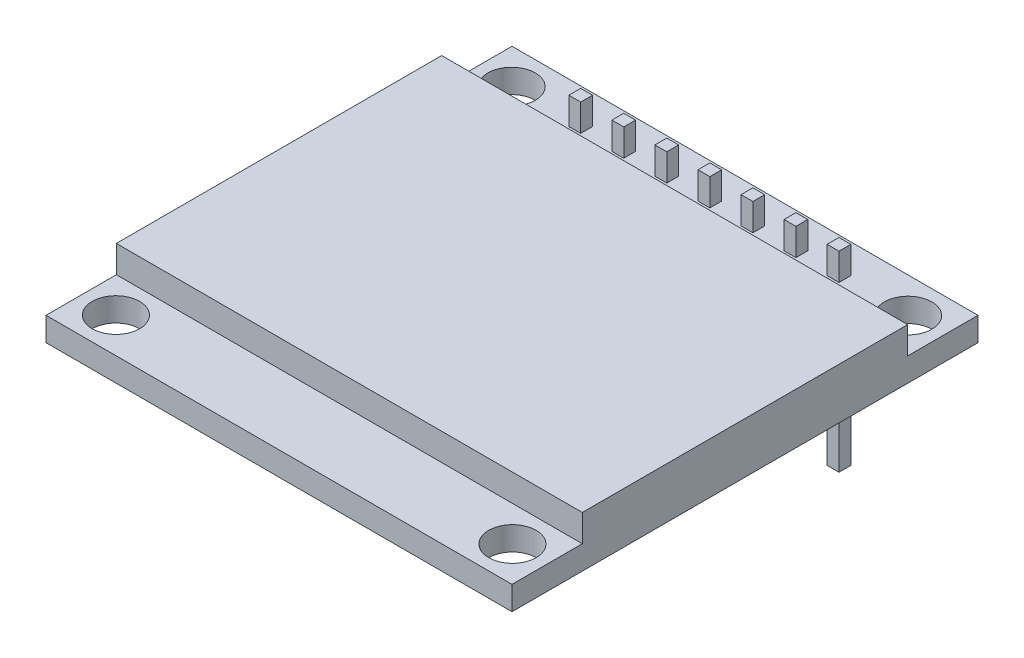
SolidWorks part; units mm, degrees
ref_plane "前视基准面" through (0, 0, 0) normal (0, 0, 1) x (1, 0, 0)
ref_plane "上视基准面" through (0, 0, 0) normal (0, 1, 0) x (1, 0, 0)
ref_plane "右视基准面" through (0, 0, 0) normal (1, 0, 0) x (0, 0, -1)
other "Configuration Table"
sketch "草图1" plane through (0, 0, 0) normal (0, 1, 0) x (1, 0, 0)
  line L0 (13.75, -23.35) -> (13.75, -27.5)
  line L1 (0, 0) -> (27.5, 0)
  line L2 (0, 0) -> (0, -27.5)
  line L3 (0, -27.5) -> (27.5, -27.5)
  line L4 (27.5, 0) -> (27.5, -27.5)
  line L9 (0, -4.15) -> (27.5, -4.15)
  line L10 (0, -4.15) -> (0, -23.35)
  line L11 (0, -23.35) -> (27.5, -23.35)
  line L12 (27.5, -4.15) -> (27.5, -23.35)
  line L13 (7.4, -0.805) -> (9.94, -0.805)
  line L18 (4.86, -0.805) -> (7.4, -0.805)
  line L19 (4.86, -0.805) -> (4.86, -3.345)
  line L20 (4.86, -3.345) -> (7.4, -3.345)
  line L21 (7.4, -0.805) -> (7.4, -3.345)
  line L22 (4.86, -0.805) -> (7.4, -3.345) construction
  line L23 (4.86, -3.345) -> (7.4, -0.805) construction
  line L24 (5.78, -2.425) -> (6.48, -2.425)
  line L25 (5.78, -2.425) -> (5.78, -1.725)
  line L26 (5.78, -1.725) -> (6.48, -1.725)
  line L27 (6.48, -2.425) -> (6.48, -1.725)
  line L28 (5.78, -2.425) -> (6.48, -1.725) construction
  line L29 (5.78, -1.725) -> (6.48, -2.425) construction
  line L30 (7.4, -0.805) -> (7.4, -3.345)
  line L31 (7.4, -3.345) -> (9.94, -3.345)
  line L32 (9.94, -0.805) -> (9.94, -3.345)
  line L33 (8.32, -2.425) -> (9.02, -2.425)
  line L34 (8.32, -2.425) -> (8.32, -1.725)
  line L35 (8.32, -1.725) -> (9.02, -1.725)
  line L36 (9.02, -2.425) -> (9.02, -1.725)
  line L37 (7.4, -0.805) -> (9.94, -3.345) construction
  line L38 (7.4, -3.345) -> (9.94, -0.805) construction
  line L39 (8.32, -2.425) -> (9.02, -1.725) construction
  line L40 (8.32, -1.725) -> (9.02, -2.425) construction
  line L41 (9.94, -0.805) -> (12.48, -0.805)
  line L42 (9.94, -0.805) -> (9.94, -3.345)
  line L43 (9.94, -3.345) -> (12.48, -3.345)
  line L44 (12.48, -0.805) -> (12.48, -3.345)
  line L45 (10.86, -2.425) -> (11.56, -2.425)
  line L46 (10.86, -2.425) -> (10.86, -1.725)
  line L47 (10.86, -1.725) -> (11.56, -1.725)
  line L48 (11.56, -2.425) -> (11.56, -1.725)
  line L49 (9.94, -0.805) -> (12.48, -3.345) construction
  line L50 (9.94, -3.345) -> (12.48, -0.805) construction
  line L51 (10.86, -2.425) -> (11.56, -1.725) construction
  line L52 (10.86, -1.725) -> (11.56, -2.425) construction
  line L53 (12.48, -0.805) -> (15.02, -0.805)
  line L54 (12.48, -0.805) -> (12.48, -3.345)
  line L55 (12.48, -3.345) -> (15.02, -3.345)
  line L56 (15.02, -0.805) -> (15.02, -3.345)
  line L57 (13.4, -2.425) -> (14.1, -2.425)
  line L58 (13.4, -2.425) -> (13.4, -1.725)
  line L59 (13.4, -1.725) -> (14.1, -1.725)
  line L60 (14.1, -2.425) -> (14.1, -1.725)
  line L61 (12.48, -0.805) -> (15.02, -3.345) construction
  line L62 (12.48, -3.345) -> (15.02, -0.805) construction
  line L63 (13.4, -2.425) -> (14.1, -1.725) construction
  line L64 (13.4, -1.725) -> (14.1, -2.425) construction
  line L65 (15.02, -0.805) -> (17.56, -0.805)
  line L66 (15.02, -0.805) -> (15.02, -3.345)
  line L67 (15.02, -3.345) -> (17.56, -3.345)
  line L68 (17.56, -0.805) -> (17.56, -3.345)
  line L69 (15.94, -2.425) -> (16.64, -2.425)
  line L70 (15.94, -2.425) -> (15.94, -1.725)
  line L71 (15.94, -1.725) -> (16.64, -1.725)
  line L72 (16.64, -2.425) -> (16.64, -1.725)
  line L73 (15.02, -0.805) -> (17.56, -3.345) construction
  line L74 (15.02, -3.345) -> (17.56, -0.805) construction
  line L75 (15.94, -2.425) -> (16.64, -1.725) construction
  line L76 (15.94, -1.725) -> (16.64, -2.425) construction
  line L77 (17.56, -0.805) -> (20.1, -0.805)
  line L78 (17.56, -0.805) -> (17.56, -3.345)
  line L79 (17.56, -3.345) -> (20.1, -3.345)
  line L80 (20.1, -0.805) -> (20.1, -3.345)
  line L81 (18.48, -2.425) -> (19.18, -2.425)
  line L82 (18.48, -2.425) -> (18.48, -1.725)
  line L83 (18.48, -1.725) -> (19.18, -1.725)
  line L84 (19.18, -2.425) -> (19.18, -1.725)
  line L85 (17.56, -0.805) -> (20.1, -3.345) construction
  line L86 (17.56, -3.345) -> (20.1, -0.805) construction
  line L87 (18.48, -2.425) -> (19.18, -1.725) construction
  line L88 (18.48, -1.725) -> (19.18, -2.425) construction
  line L89 (20.1, -0.805) -> (22.64, -0.805)
  line L90 (20.1, -0.805) -> (20.1, -3.345)
  line L91 (20.1, -3.345) -> (22.64, -3.345)
  line L92 (22.64, -0.805) -> (22.64, -3.345)
  line L93 (21.02, -2.425) -> (21.72, -2.425)
  line L94 (21.02, -2.425) -> (21.02, -1.725)
  line L95 (21.02, -1.725) -> (21.72, -1.725)
  line L96 (21.72, -2.425) -> (21.72, -1.725)
  line L97 (20.1, -0.805) -> (22.64, -3.345) construction
  line L98 (20.1, -3.345) -> (22.64, -0.805) construction
  line L99 (21.02, -2.425) -> (21.72, -1.725) construction
  line L100 (21.02, -1.725) -> (21.72, -2.425) construction
  line L101 (23.6355, 0) -> (23.6355, -4.15)
  circle A0 centre (2.05, -2.075) radius 1.4
  circle A1 centre (25.45, -2.075) radius 1.4
  circle A2 centre (2.05, -25.425) radius 1.4
  circle A3 centre (25.45, -25.425) radius 1.4
  point P9 (0, -13.75)
  point P10 (0, -13.75)
  point P19 (13.75, -25.425)
  point P20 (6.13, -2.075)
  point P25 (6.13, -2.075)
  point P32 (23.6355, -2.075)
  point P33 (8.67, -2.075)
  point P38 (8.67, -2.075)
  point P43 (11.21, -2.075)
  point P48 (11.21, -2.075)
  point P53 (13.75, -2.075)
  point P58 (13.75, -2.075)
  point P63 (16.29, -2.075)
  point P68 (16.29, -2.075)
  point P73 (18.83, -2.075)
  point P78 (18.83, -2.075)
  point P83 (21.37, -2.075)
  point P88 (21.37, -2.075)
  dimension "D3" = 2.8
  dimension "D9" = 0.7
  dimension "D1" = 27.5
  dimension "D2" = 19.2
  dimension "D5" = 2.05
  dimension "D7" = 2.05
  dimension "D8" = 2.54
  dimension "D10" = 7
extrude "凸台-拉伸1" add sketch "草图1" along normal blind 1.4 contours L3 L4 L1 L2 | A0 | A1 | A2 | A3
extrude "凸台-拉伸2" add sketch "草图1<3>" along normal blind 3 contours L9 L12 L11 L10
sketch "草图1<3>" plane through (0, 0, 0) normal (0, 1, 0) x (1, 0, 0) same geometry as "草图1"
extrude "凸台-拉伸3" add sketch "草图1<4>" against normal blind 2.54 contours L89 L92 L91 L90 | L77 L80 L79 L78 | L65 L68 L67 L66 | L53 L56 L55 L54 | L41 L44 L43 L42 | L13 L32 L31 L30 | L18 L21 L20 L19
sketch "草图1<4>" plane through (0, 0, 0) normal (0, 1, 0) x (1, 0, 0) same geometry as "草图1"
extrude "凸台-拉伸4" add sketch "草图1<5>" against normal blind 11.3 from surface contours L95 L96 L93 L94 | L83 L84 L81 L82 | L71 L72 L69 L70 | L59 L60 L57 L58 | L47 L48 L45 L46 | L35 L36 L33 L34 | L26 L27 L24 L25 starting at face at (13.75, 3, 13.75)
sketch "草图1<5>" plane through (0, 0, 0) normal (0, 1, 0) x (1, 0, 0) same geometry as "草图1"
